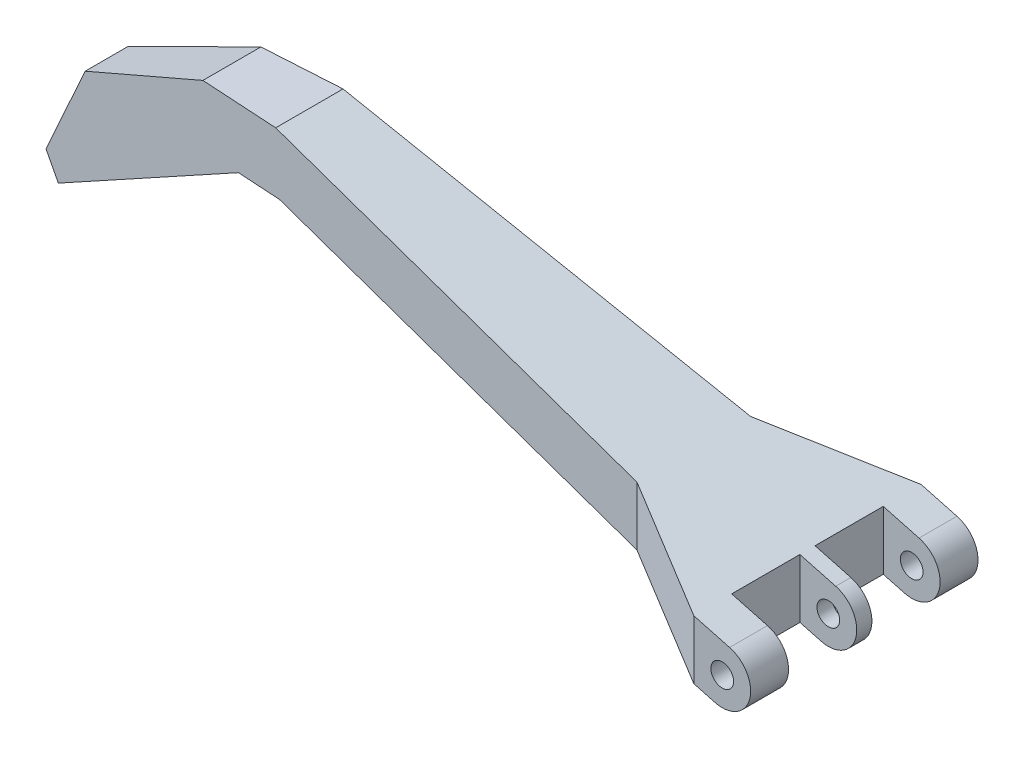
SolidWorks part; units mm, degrees
material "ABS"
ref_plane "Front Plane" through (0, 0, 0) normal (0, 0, 1) x (1, 0, 0)
ref_plane "Top Plane" through (0, 0, 0) normal (0, 1, 0) x (1, 0, 0)
ref_plane "Right Plane" through (0, 0, 0) normal (1, 0, 0) x (0, 0, -1)
sketch "Sketch3" plane through (0, 0, 0) normal (0, 0, 1) x (1, 0, 0)
  line L0 (0.9706, 3.6222) -> (-69.4823, 22.5)
  line L1 (-69.4823, 22.5) -> (-79.7011, 22.5)
  line L2 (-79.7011, 22.5) -> (-96.234, 14.7906)
  line L3 (-96.234, 14.7906) -> (-101.7321, 3)
  line L4 (-101.7321, 3) -> (-100, 0)
  line L5 (-100, 0) -> (-74.715, 14.5983)
  line L6 (-74.715, 14.5983) -> (-68.9706, 14.5983)
  line L7 (-68.9706, 14.5983) -> (-0.9706, -3.6222)
  line L8 (-0.9706, -3.6222) -> (0.9706, 3.6222) construction
  line L9 (-5.6356, -2.3722) -> (-3.6945, 4.8722) construction
  line L10 (-100, 0) -> (0, 0) construction
  circle A0 centre (0, 0) radius 1.5
  arc A2 (-0.9706, -3.6222) -> (0.9706, 3.6222) centre (0, 0) ccw
  point P14 (-5, 0)
  dimension "D2" = 3
  dimension "D1" = 100
  dimension "D3" = 7.5
  dimension "D4" = 68
  dimension "D5" = 30
  dimension "D6" = 15
  dimension "D7" = 125
  dimension "D8" = 5.498
  dimension "D9" = 3
  dimension "D10" = 155
  dimension "D11" = 22.5
sketch "Sketch4" plane through (0, 0, 0) normal (1, 0, 0) x (0, 0, -1)
  line L0 (-15, 0) -> (15, 0)
  point P4 (0, 0)
  dimension "D1" = 30
ref_plane "Plane1" through (-101.7321, 0, 0) normal (1, 0, 0) x (0, 0, -1)
sketch "Sketch5" plane through (-101.7321, 0, 0) normal (1, 0, 0) x (0, 0, -1)
  line L0 (2.5, 0) -> (-2.5, 0)
  point P4 (0, 0)
  dimension "D1" = 5
sketch "Sketch14" plane through (0, 0, 0) normal (0, 0, 1) x (1, 0, 0)
  line L0 (-153.9208, -162.5929) -> (-22.7793, -162.5929) construction
extrude "Boss-Extrude2" add sketch "Sketch3" along direction (0, 0, -1) on the side against the normal up to vertex (15 mm away) and the other way up to vertex (15 mm away) up to point (0, 0, -15) other way up to point (0, 0, 15)
sketch "Sketch12" plane through (0, 0, 0) normal (0, 1, 0) x (1, 0, 0)
  line L0 (-101.7321, 2.5) -> (-101.7321, -2.5) construction
  line L1 (-101.7321, 2.5) -> (-3.75, 2.5) construction
  line L2 (-101.7321, 2.5) -> (-101.7321, -2.5)
  line L3 (-3.75, -15) -> (-3.75, 15)
  line L4 (-101.7321, 2.5) -> (-3.75, 15) construction
  line L5 (-101.7321, -2.5) -> (-3.75, -15) construction
  line L6 (-101.7321, 0) -> (0, 0) construction
  line L7 (0, -15) -> (0, 15) construction
  line L8 (0, -15) -> (0, 15) construction
  line L9 (-101.7321, 2.5) -> (-18.75, 7.5)
  line L10 (-18.75, 7.5) -> (-3.75, 15)
  line L11 (-18.75, -7.5) -> (-3.75, -15)
  line L12 (-101.7321, -2.5) -> (-18.75, -7.5)
  dimension "D1" = 3.75
  dimension "D2" = 7.5
  dimension "D3" = 15
extrude "Cut-Extrude2" cut sketch "Sketch12" along normal through all and the other way through all flip side to cut contours L2 L12 L11 L3 L10 L9 | L3 L10 L9 L2 L12 L11 region at (-40.9198, 0, 0)
sketch "Sketch13" plane through (0, 0, 0) normal (0, 0, 1) x (1, 0, 0)
  line L0 (-3.75, 4.8871) -> (-3.75, -2.8775) construction
  line L1 (-3.75, 4.8871) -> (-3.75, -2.8775)
  line L8 (0.9706, 3.6222) -> (-3.75, 4.8871)
  line L9 (-0.9706, -3.6222) -> (-3.75, -2.8775)
  arc A0 (-0.9706, -3.6222) -> (0.9706, 3.6222) centre (0, 0) ccw construction
  circle A1 centre (0, 0) radius 1.5 construction
  arc A2 (-0.9706, -3.6222) -> (0.9706, 3.6222) centre (0, 0) ccw
  circle A3 centre (0, 0) radius 1.5
extrude "Boss-Extrude3" add sketch "Sketch13" along direction (0, 0, 1) on the side of the normal up to vertex (15 mm away) and the other way up to vertex (15 mm away) up to point (-3.75, 4.8871, 15) other way up to point (-3.75, 4.8871, -15)
sketch "Sketch16" plane through (0.9706, 3.6222, 0) normal (0.2588, 0.9659, 0) x (0.9659, -0.2588, 0)
  line L0 (3.75, -15) -> (3.75, 15) construction
  line L1 (3.75, -15) -> (3.75, 15) construction
  line L2 (3.75, 15) -> (0, 15) construction
  line L3 (0, -15) -> (3.75, -15) construction
  line L4 (3.75, 15) -> (0, 15) construction
  line L5 (0, -15) -> (3.75, -15) construction
  line L6 (0, 15) -> (-4.8871, 15) construction
  line L7 (0, -15) -> (-4.8871, -15) construction
  line L8 (0, 15) -> (-4.8871, 15) construction
  line L9 (0, -15) -> (-4.8871, -15) construction
  line L10 (-4.8871, -15) -> (-4.8871, 15) construction
  line L11 (3.75, 0) -> (-4.8871, 0) construction
  line L12 (3.75, -1) -> (-4.8871, -1)
  line L13 (-4.8871, 1) -> (3.75, 1)
  line L14 (-4.8871, -10) -> (3.75, -10)
  line L15 (-4.8871, 10) -> (3.75, 10)
  line L16 (3.75, -10) -> (-4.8871, -10)
  line L17 (-4.8871, -10) -> (-4.8871, -1)
  line L18 (3.75, -1) -> (3.75, -10)
  line L19 (-4.8871, 10) -> (-4.8871, 1)
  line L20 (3.75, 1) -> (3.75, 10)
  line L21 (3.75, -1) -> (3.75, -10)
  line L22 (-4.8871, -10) -> (-4.8871, -1)
  line L23 (0, -15) -> (0, 15) construction
  line M12 (0, -15) -> (0, 15)
  dimension "D1" = 2
  dimension "D2" = 9
extrude "Cut-Extrude8" cut sketch "Sketch16" along direction (0, -1, 0) on the side against the normal up to surface (7.5 mm away) contours L15 L19 L13 M12 | L17 L14 L12 M12 | L18 L12 L14 M12 | L13 L20 L15 M12 region at (2.7817, 3.1369, 5.5) region at (-1.3897, 4.2547, -5.5) region at (2.7817, 3.1369, -5.5) region at (-1.3897, 4.2547, 5.5) up to face at (-23.1103, 2.3101, 0)
sketch "Sketch17" [suppressed] plane through (-25, 43.3013, 0) normal (0.5, -0.866, 0) x (0.866, 0.5, 0)
  line L0 (-86.6025, 0) -> (-57.4059, 0) construction
  line L1 (-86.6025, -2.606) -> (-86.6025, 2.606) construction
  line L2 (-57.4059, -4.1528) -> (-57.4059, 4.1528) construction
  line L3 (-86.6025, 2.606) -> (-57.4059, 4.1528) construction
  circle A0 centre (-85.1025, 1.1833) radius 0.75
  circle A1 centre (-85.1025, -1.1833) radius 0.75
  dimension "D1" = 1.5
  dimension "D2" = 1.5
  dimension "D3" = 1.5
extrude "Boss-Extrude4" [suppressed] add sketch "Sketch17" along normal blind 6 draft 12
